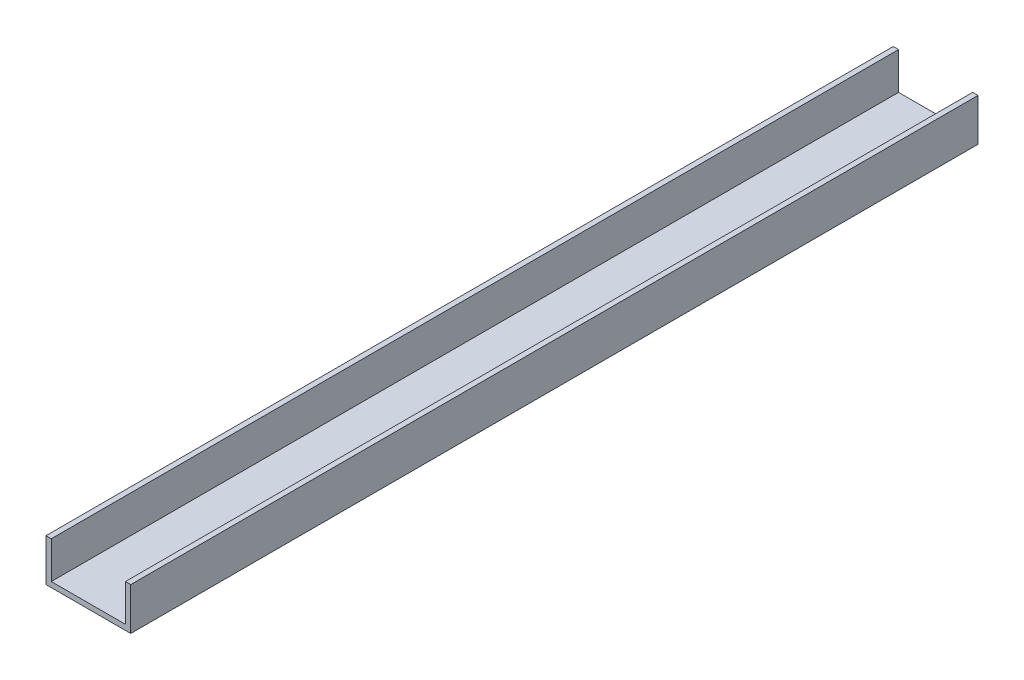
SolidWorks part; units mm, degrees
material "6063-T6"
ref_plane "Front" through (0, 0, 0) normal (0, 0, 1) x (1, 0, 0)
ref_plane "Top" through (0, 0, 0) normal (0, 1, 0) x (1, 0, 0)
ref_plane "Right" through (0, 0, 0) normal (1, 0, 0) x (0, 0, -1)
sketch "Sketch1" plane through (0, 0, 0) normal (0, 0, 1) x (1, 0, 0)
  line L0 (47.625, 3.175) -> (47.625, 25.4)
  line L1 (0, 0) -> (50.8, 0)
  line L2 (0, 0) -> (0, 25.4)
  line L4 (50.8, 0) -> (50.8, 25.4)
  line L5 (3.175, 3.175) -> (47.625, 3.175)
  line L6 (3.175, 3.175) -> (3.175, 25.4)
  line L7 (50.8, 25.4) -> (47.625, 25.4)
  line L8 (0, 25.4) -> (3.175, 25.4)
  dimension "D1" = 25.4
  dimension "D2" = 50.8
  dimension "D3" = 3.175
extrude "Boss-Extrude1" add sketch "Sketch1" along normal blind 508
